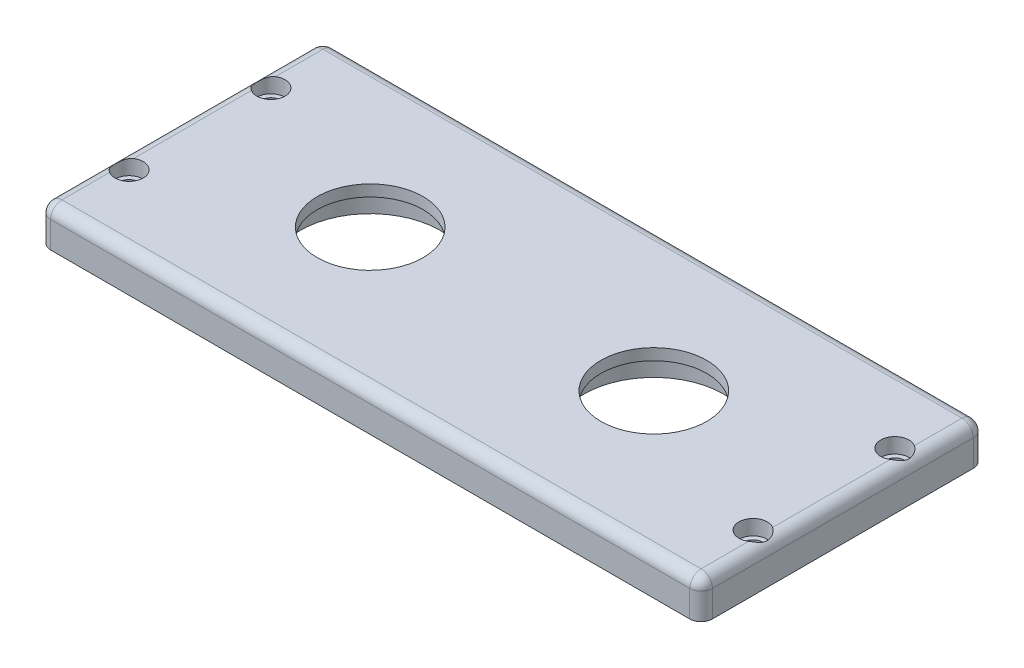
SolidWorks part; units mm, degrees
ref_plane "Front Plane" through (0, 0, 0) normal (0, 0, 1) x (1, 0, 0)
ref_plane "Top Plane" through (0, 0, 0) normal (0, 1, 0) x (1, 0, 0)
ref_plane "Right Plane" through (0, 0, 0) normal (1, 0, 0) x (0, 0, -1)
sketch "Sketch1" plane through (0, 0, 0) normal (0, 1, 0) x (1, 0, 0)
  line L0 (0, 0) -> (-52231.4268, 0) construction
  line L1 (0, 0) -> (0, -52231.4268) construction
  line L3 (-87.5, 37.5) -> (87.5, 37.5)
  line L4 (-87.5, 37.5) -> (-87.5, -37.5)
  line L5 (-87.5, -37.5) -> (87.5, -37.5)
  line L6 (87.5, 37.5) -> (87.5, -37.5)
  line L7 (-87.5, 37.5) -> (87.5, -37.5) construction
  line L8 (-87.5, -37.5) -> (87.5, 37.5) construction
  point P5 (0, 0)
  dimension "D1" = 75
  dimension "D2" = 175
extrude "Boss-Extrude1" add sketch "Sketch1" along normal blind 10
sketch "Sketch2" plane through (0, 10, 0) normal (0, 1, 0) x (1, 0, 0)
  line L0 (0, 0) -> (-50000, 0) construction
  line L1 (0, 0) -> (0, -50000) construction
  line L2 (-82.5, 25) -> (-82.5, -49975) construction
  line L4 (-87.5, 37.5) -> (-87.5, -37.5) construction
  circle A0 centre (-82.5, 18.75) radius 3.75
  circle A1 centre (-82.5, -18.75) radius 3.75
  circle A2 centre (82.5, -18.75) radius 3.75
  circle A3 centre (82.5, 18.75) radius 3.75
  dimension "D2" = 7.5
  dimension "D3" = 18.75
  dimension "D1" = 5
extrude "Cut-Extrude1" cut sketch "Sketch2" against normal blind 4
sketch "Sketch3" plane through (0, 10, 0) normal (0, 1, 0) x (1, 0, 0)
  line L0 (0, 0) -> (50000, 0) construction
  line L1 (0, 0) -> (0, -50000) construction
  circle A0 centre (-82.5, 18.75) radius 2.5
  circle A1 centre (-82.5, -18.75) radius 2.5
  circle A2 centre (82.5, -18.75) radius 2.5
  circle A3 centre (82.5, 18.75) radius 2.5
  dimension "D1" = 5
extrude "Cut-Extrude2" cut sketch "Sketch3" against normal through all
sketch "Sketch4" plane through (0, 10, 0) normal (0, 1, 0) x (1, 0, 0)
  line L0 (0, 0) -> (-50000, 0) construction
  line L1 (0, 0) -> (0, -50000) construction
  circle A0 centre (-37.5, 0) radius 14
  dimension "D1" = 28
  dimension "D2" = 37.5
extrude "Cut-Extrude3" cut sketch "Sketch4" against normal through all
sketch "Sketch5" plane through (0, 0, 0) normal (0, -1, 0) x (1, 0, 0)
  line L0 (0, 0) -> (-50000, 0) construction
  line L1 (0, 0) -> (0, -50000) construction
  circle A0 centre (-37.5, 0) radius 18.5
  dimension "D1" = 37
extrude "Cut-Extrude4" cut sketch "Sketch5" against normal blind 7
mirror "Mirror1" about plane through (0, 0, 0) normal (1, 0, 0) of "Cut-Extrude4", "Cut-Extrude3"
fillet "Fillet1" radius 3 8 edges at (87.5, 10, 0) (0, 10, 37.5) (-87.5, 10, 0) (0, 10, -37.5) (-87.5, 5, -37.5) (87.5, 5, -37.5) (87.5, 5, 37.5) (-87.5, 5, 37.5)
